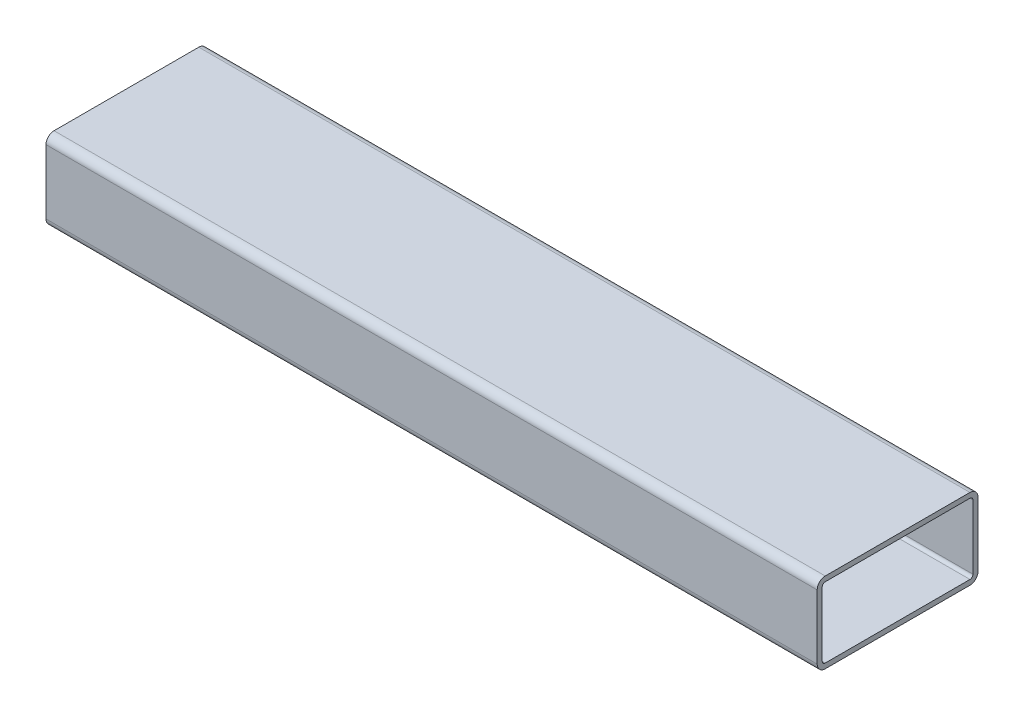
SolidWorks part; units mm, degrees
material "6061 Alloy"
ref_plane "Front" through (0, 0, 0) normal (0, 0, 1) x (1, 0, 0)
ref_plane "Top" through (0, 0, 0) normal (0, 1, 0) x (1, 0, 0)
ref_plane "Right" through (0, 0, 0) normal (1, 0, 0) x (0, 0, -1)
sketch "Sketch1" plane through (0, 0, 0) normal (1, 0, 0) x (0, 0, -1)
  line L1 (-2.54, 0) -> (-48.26, 0)
  line L2 (0, 2.54) -> (0, 22.86)
  line L3 (-2.54, 25.4) -> (-48.26, 25.4)
  line L4 (-50.8, 2.54) -> (-50.8, 22.86)
  arc A0 (-50.8, 2.54) -> (-48.26, 0) centre (-48.26, 2.54) ccw
  arc A1 (-2.54, 0) -> (0, 2.54) centre (-2.54, 2.54) ccw
  arc A2 (0, 22.86) -> (-2.54, 25.4) centre (-2.54, 22.86) ccw
  arc A3 (-48.26, 25.4) -> (-50.8, 22.86) centre (-48.26, 22.86) ccw
  point P7 (-50.8, 0)
  point P10 (0, 0)
  point P13 (0, 25.4)
  dimension "D3" = 2.54
  dimension "D1" = 25.4
  dimension "D2" = 50.8
extrude "Extrude-Thin1" add sketch "Sketch1" against normal blind 243.6368 thin thin type one direction reverse wall 1.5875
sketch "Sketch3" plane through (0, 25.4, 0) normal (0, 1, 0) x (1, 0, 0)
  line L0 (0, 49.2125) -> (79.6022, 243.0747)
  line L1 (0, -1.5875) -> (25.4, -1.5875)
  line L2 (0, -1.5875) -> (0, 49.2125)
  line L3 (0, 49.2125) -> (25.4, 49.2125)
  line L4 (25.4, -1.5875) -> (25.4, 49.2125)
  line L5 (79.6022, 243.0747) -> (126.5949, 223.7789)
  line L6 (126.5949, 223.7789) -> (34.0567, -1.5875)
  line L7 (71.7537, 223.9604) -> (118.7463, 204.6646) construction
  line L8 (95.25, 214.3125) -> (0, 214.3125)
  line L9 (0, 49.2125) -> (0, 289.0515)
  line L10 (25.4, -1.5875) -> (34.0567, -1.5875)
  circle A0 centre (95.25, 214.3125) radius 14.3129
  point P11 (95.25, 214.3125)
  dimension "D4" = 28.6258
  dimension "D5" = 6.35
  dimension "D1" = 25.4
  dimension "D2" = 50.8
  dimension "D3" = 50.8
  dimension "D6" = 95.25
  dimension "D7" = 165.1
  dimension "D8" = 243.6254
  dimension "D9" = 209.5687
sketch "Sketch4" plane through (0, 25.4, 0) normal (0, 1, 0) x (1, 0, 0)
  circle A0 centre (-20.088, -26.9772) radius 13.1435
